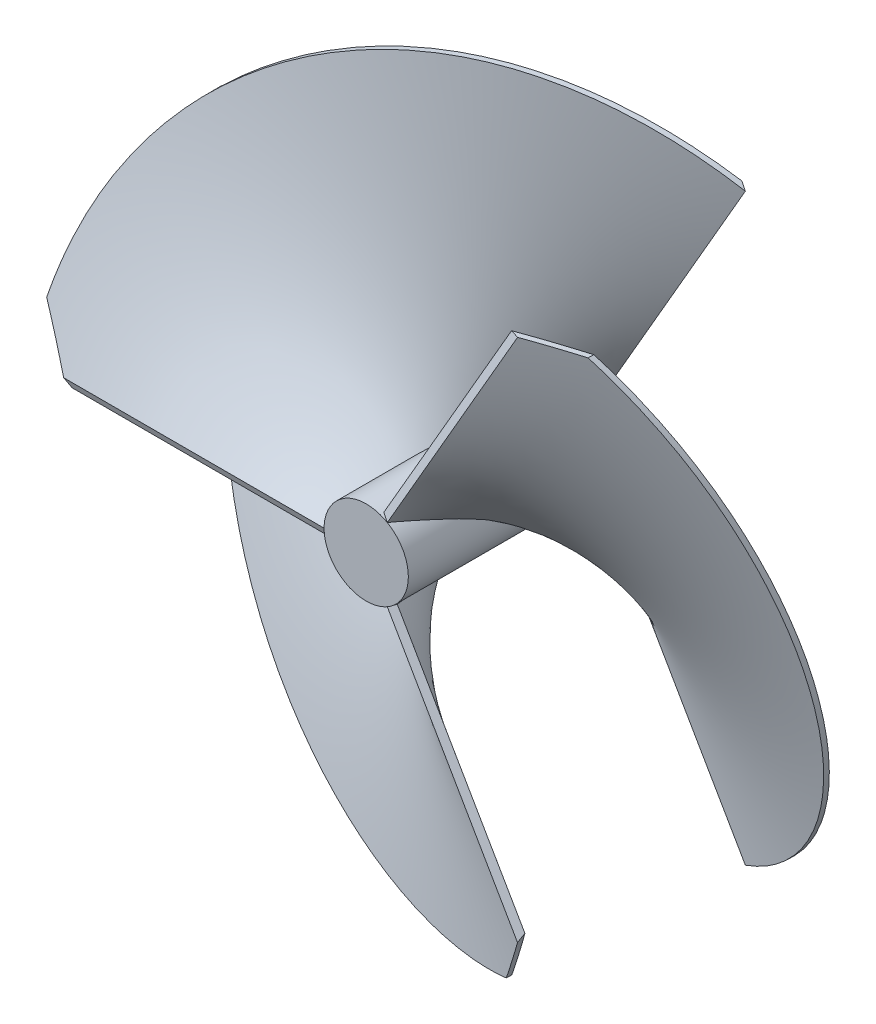
SolidWorks part; units mm, degrees
ref_plane "前视基准面" through (0, 0, 0) normal (0, 0, 1) x (1, 0, 0)
ref_plane "上视基准面" through (0, 0, 0) normal (0, 1, 0) x (1, 0, 0)
ref_plane "右视基准面" through (0, 0, 0) normal (1, 0, 0) x (0, 0, -1)
sketch "草图1" plane through (0, 0, 0) normal (0, 0, 1) x (1, 0, 0)
  circle A0 centre (0, 0) radius 10
extrude "凸台-拉伸1" add sketch "草图1" along normal blind 50
sketch "草图2" plane through (0, 0, 0) normal (0, 0, -1) x (-1, 0, 0)
  circle A0 centre (0, 0) radius 10
curve "螺旋线/涡状线1" pitch 150 height 49.995 radius 10 centre (0, 0, 0) axis (0, 0, 1) start towards (-1, 0, 0)
ref_plane "基准面1" through (-10, 0, 0) normal (0, -0.3864, 0.9224) x (1, 0, 0)
sketch "草图3" plane through (-10, 0, 0) normal (0, -0.3864, 0.9224) x (1, 0, 0)
  line L1 (0, 0) -> (-70, 0)
  line L2 (0, 0) -> (0, -2)
  line L3 (0, -2) -> (-70, -2)
  line L4 (-70, 0) -> (-70, -2)
  ellipse E0 centre (10, 0) end of major axis (20, 0) minor radius 9.2235 construction
  dimension "D1" = 70
  dimension "D2" = 2
sweep "扫描1" add profiles "草图3" path "螺旋线/涡状线1"
ref_plane "基准面2" through (0, 0, 50) normal (0, 0, 1) x (1, 0, 0)
sketch "草图5" plane through (0, 0, 50) normal (0, 0, 1) x (1, 0, 0)
  line L2 (-45, 0) -> (-60.9312, -2.8644)
  line L3 (-10, 0) -> (-80, 0) construction
  line L4 (-60.9312, -2.8644) -> (-67.6563, -6.3871)
  line L5 (-67.6563, -6.3871) -> (-71.8195, -11.511)
  line L6 (-71.8195, -11.511) -> (-74.3815, -18.8766)
  line L7 (-74.3815, -18.8766) -> (-77.2637, -34.5686)
  line L8 (-77.2637, -34.5686) -> (-64.2938, -73.9586)
  line L9 (-64.2938, -73.9586) -> (-32.0055, -85.1893)
  line L10 (-32.0055, -85.1893) -> (9.2023, -90.6114)
  line L11 (9.2023, -90.6114) -> (28.7373, -76.5206)
  line L12 (28.7373, -76.5206) -> (38.0281, -57.9756)
  line L13 (38.0281, -57.9756) -> (32.4089, -26.7226)
  line L14 (32.4089, -26.7226) -> (7.4642, 20.8992)
  line L15 (7.4642, 20.8992) -> (-39.9754, 12.3697)
  line L16 (-39.9754, 12.3697) -> (-45, 0)
extrude "切除-拉伸2" cut sketch "草图5" against normal blind 40 and the other way blind 40 flip side to cut
pattern_circular "阵列(圆周)1" count 3 every 120 about axis through (0, 0, 50) along (0, 0, -1) of bodies 120
